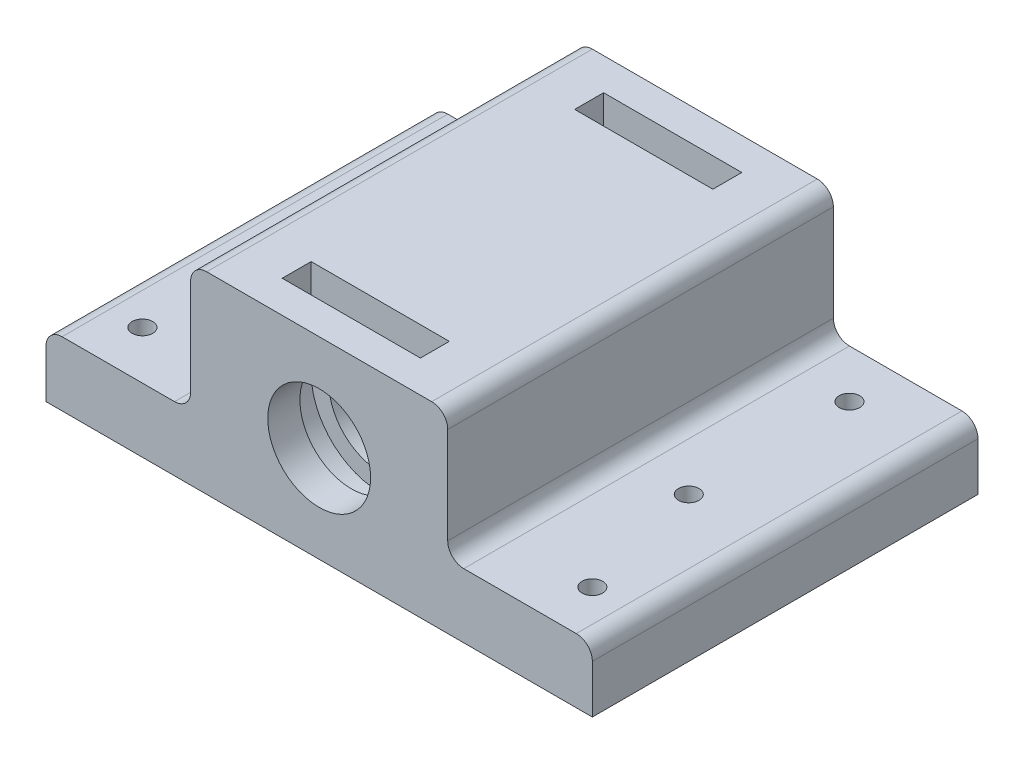
SolidWorks part; units mm, degrees
ref_plane "Front Plane" through (0, 0, 0) normal (0, 0, 1) x (1, 0, 0)
ref_plane "Top Plane" through (0, 0, 0) normal (0, 1, 0) x (1, 0, 0)
ref_plane "Right Plane" through (0, 0, 0) normal (1, 0, 0) x (0, 0, -1)
sketch "Sketch2" plane through (0, 0, 0) normal (0, 0, 1) x (1, 0, 0)
  line L0 (0, 30) -> (85, 0) construction
  line L1 (0, 0) -> (85, 0)
  line L2 (0, 0) -> (0, 30)
  line L3 (0, 30) -> (85, 30)
  line L4 (85, 0) -> (85, 30)
  line L5 (42.5, 30) -> (42.5, 15) construction
  line L6 (62.5, 30) -> (85, 30)
  line L7 (62.5, 30) -> (62.5, 10)
  line L8 (62.5, 10) -> (85, 10)
  line L9 (85, 30) -> (85, 10)
  line L10 (22.5, 10) -> (0, 10)
  line L11 (22.5, 30) -> (22.5, 10)
  circle A0 centre (42.5, 15) radius 8
  dimension "D3" = 16
  dimension "D1" = 30
  dimension "D2" = 85
  dimension "D4" = 20
  dimension "D5" = 22.5
extrude "Boss-Extrude1" add sketch "Sketch2" along normal blind 15 and the other way blind 45 contours L3 L11 L10 L2 L1 L4 L8 L7 A0 region at (0.9014, 5, 0)
sketch "Sketch3" plane through (0, 0, 0) normal (0, 1, 0) x (1, 0, 0)
  line L0 (0, -7.5) -> (85, -7.5) construction
  line L2 (22.5, 45) -> (62.5, 45) construction
  line L3 (42.5, 45) -> (42.5, -15) construction
  line L10 (0, 45) -> (0, -15) construction
  line L11 (85, 45) -> (85, -15) construction
  line L12 (22.5, -15) -> (62.5, -15) construction
  circle A0 centre (7.5, -7.5) radius 1.6
  circle A1 centre (77.5, -7.5) radius 1.6
  circle A2 centre (72.5, 12.5) radius 1.6
  circle A3 centre (12.5, 12.5) radius 1.6
  circle A4 centre (72.5, 37.5) radius 1.6
  circle A5 centre (12.5, 37.5) radius 1.6
  dimension "D1" = 3.2
  dimension "D3" = 3.2
  dimension "D4" = 20
  dimension "D6" = 7.5
  dimension "D7" = 25
  dimension "D2" = 70
  dimension "D5" = 30
extrude "Cut-Extrude1" cut sketch "Sketch3" along normal through all both and the other way through all contours A2 | A3 | A0 | A1 | A5 | A4 region at (7.5, 0, 7.5) region at (77.5, 0, 7.5) region at (72.5, 0, -12.5) region at (12.5, 0, -12.5) region at (72.5, 0, -37.5) region at (12.5, 0, -37.5)
fillet "Fillet1" radius 2.5 6 edges at (62.5, 10, -15) (22.5, 10, -15) (85, 10, -15) (0, 10, -15) (62.5, 30, -15) (22.5, 30, -15)
ref_plane "Plane1" through (0, 0, 10) normal (0, 0, 1) x (1, 0, 0)
sketch "Sketch5" plane through (0, 0, 0) normal (0, 0, 1) x (1, 0, 0)
  line L0 (42.5, 15) -> (42.5, 30) construction
  line L1 (25, 30) -> (60, 30) construction
  line L3 (31.75, 30) -> (31.75, 15)
  line L4 (31.75, 15) -> (53.25, 15) construction
  line L5 (53.25, 15) -> (53.25, 30)
  line L6 (53.25, 30) -> (31.75, 30)
  arc A0 (53.25, 15) -> (31.75, 15) centre (42.5, 15) cw
  circle A1 centre (42.5, 15) radius 8 construction
  circle A2 centre (42.5, 15) radius 8 construction
  point P5 (42.5, 4.25)
  point P12 (42.5, 15)
  dimension "D1" = 10.75
  dimension "D2" = 21.5
extrude "Cut-Extrude5" cut sketch "Sketch5" against normal blind 4.5 from surface starting at plane "Plane1"
ref_plane "Plane2" through (0, 0, -40) normal (0, 0, -1) x (-1, 0, 0)
extrude "Cut-Extrude6" cut sketch "Sketch5<2>" along normal blind 4.5 from surface starting at plane "Plane2"
sketch "Sketch5<2>" plane through (0, 0, 0) normal (0, 0, 1) x (1, 0, 0) same geometry as "Sketch5"
